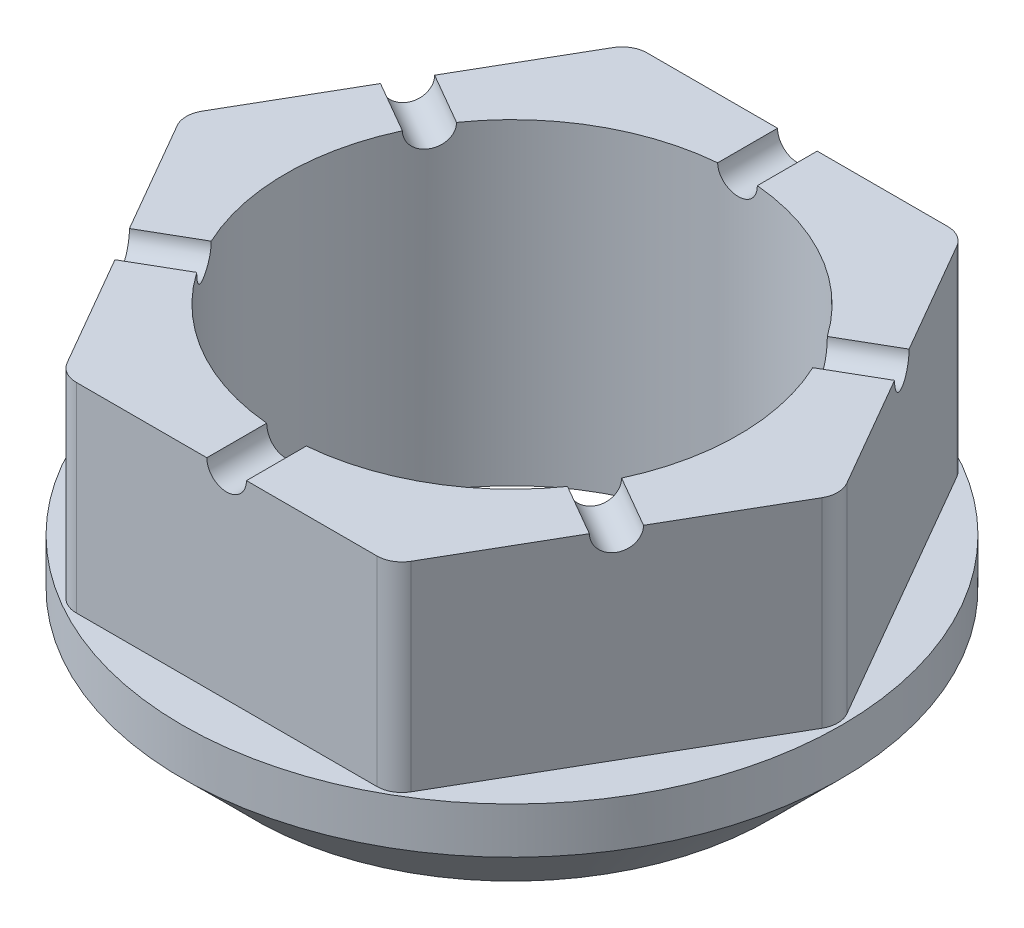
SolidWorks part; units mm, degrees
note: '?' marks a value the reader was unsure of.
material "7075-T6 (SN)"
ref_plane "X-Y Datum" through (0, 0, 0) normal (0, 0, 1) x (1, 0, 0)
ref_plane "X-Z Datum" through (0, 0, 0) normal (0, 1, 0) x (1, 0, 0)
ref_plane "Y-Z Datum" through (0, 0, 0) normal (1, 0, 0) x (0, 0, -1)
sketch "Sketch1" plane through (0, 0, 0) normal (1, 0, 0) x (0, 0, -1)
  line L0 (0, 0) -> (0, 50000) construction
  line L1 (0, 0) -> (-50000, 0) construction
  line L2 (-22.6695, -31.75) -> (-22.6695, 0)
  line L3 (-22.6695, 0) -> (-33, 0)
  line L4 (-33, 0) -> (-33, -24.6194)
  line L6 (-33, -24.6194) -> (-25.8445, -31.75)
  line L7 (-25.8445, -31.75) -> (-22.6695, -31.75)
  dimension "D1" = 66
  dimension "D2" = 3.175
  dimension "D3" = 31.75
  dimension "D4" = 45.339
  dimension "D5" = 45.1
  dimension "D6" = 24.6194
revolve "Revolve1" add sketch "Sketch1" angle 360 about L0
ref_axis "Axis1" through (0, 2.4756, 0) along (0, -1, 0)?
thread "Thread1" [suppressed] pitch 2.1167 start angle 0, offset 0, length 0, pitch 2.1167, diameter 45.339
ref_plane "Plane1" through (22.6695, -31.75, 0) normal (0, 0, 1) x (1, 0, 0)
sketch "Thread Profile1" plane through (22.6695, -31.75, 0) normal (0, 0, 1) x (1, 0, 0)
  line L0 (0, 0) -> (0, 2.1167) construction
  line L1 (0, 0) -> (1.1457, 0.6615)
  line L2 (1.1457, 0.6615) -> (1.1457, 0.926)
  line L3 (1.1457, 0.926) -> (0, 1.5875)
  line L4 (1.1457, 0.7937) -> (0, 0.7937) construction
  line L11 (0, 0) -> (0, 1.5875)
  point P2 (0, 0)
  dimension "Pitch" = 2.1167
  dimension "Profile_Angle" = 60
  dimension "Profile_Land" = 0.2646
  dimension "Profile_Height" = 1.1457
sketch "Sketch4" plane through (0, 0, 0) normal (0, 1, 0) x (1, 0, 0)
  line L1 (16.5, 28.5788) -> (-16.5, 28.5788)
  line L2 (-16.5, 28.5788) -> (-33, 0)
  line L3 (-33, 0) -> (-16.5, -28.5788)
  line L4 (-16.5, -28.5788) -> (16.5, -28.5788)
  line L5 (16.5, -28.5788) -> (33, 0)
  line L6 (33, 0) -> (16.5, 28.5788)
  circle A0 centre (0, 0) radius 28.5788 construction
  circle A1 centre (0, 0) radius 33 construction
  circle A2 centre (0, 0) radius 33 construction
  point P14 (0, 28.5788)
  circle M16 centre (0, 0) radius 33
extrude "Cut-Extrude5" cut sketch "Sketch4" against normal blind 20 contours L6 L5 L4 L3 L2 L1 M16 | L1 M16 | L2 M16 | L3 M16 | L4 M16 | L5 M16
fillet "Fillet4" radius 2.5 6 edges at (16.5, -10, 28.5788) (33, -10, 0) (16.5, -10, -28.5788) (-16.5, -10, -28.5788) (-33, -10, 0) (-16.5, -10, 28.5788)
sketch "Sketch7" plane through (0, 0, 0) normal (0, 0, 1) x (1, 0, 0)
  circle A1 centre (0, 0) radius 1.9844
  dimension "D2" = 3.9688
extrude "Cut-Extrude6" cut sketch "Sketch7" along normal through all both and the other way through all from surface at -28.5788 starting at face at (0, -10, -28.5788)
pattern_circular "CirPattern2" count 6 over 360 about axis through (0, 0, 0) along (0, -1, 0) of "Cut-Extrude6"
move or copy body "Body-Move/Copy1" [suppressed] parameters "D1"=0, "D2"=0, "D3"=0
move or copy body "Body-Move/Copy2" [suppressed] parameters "D1"=0, "D2"=0, "D3"=0
